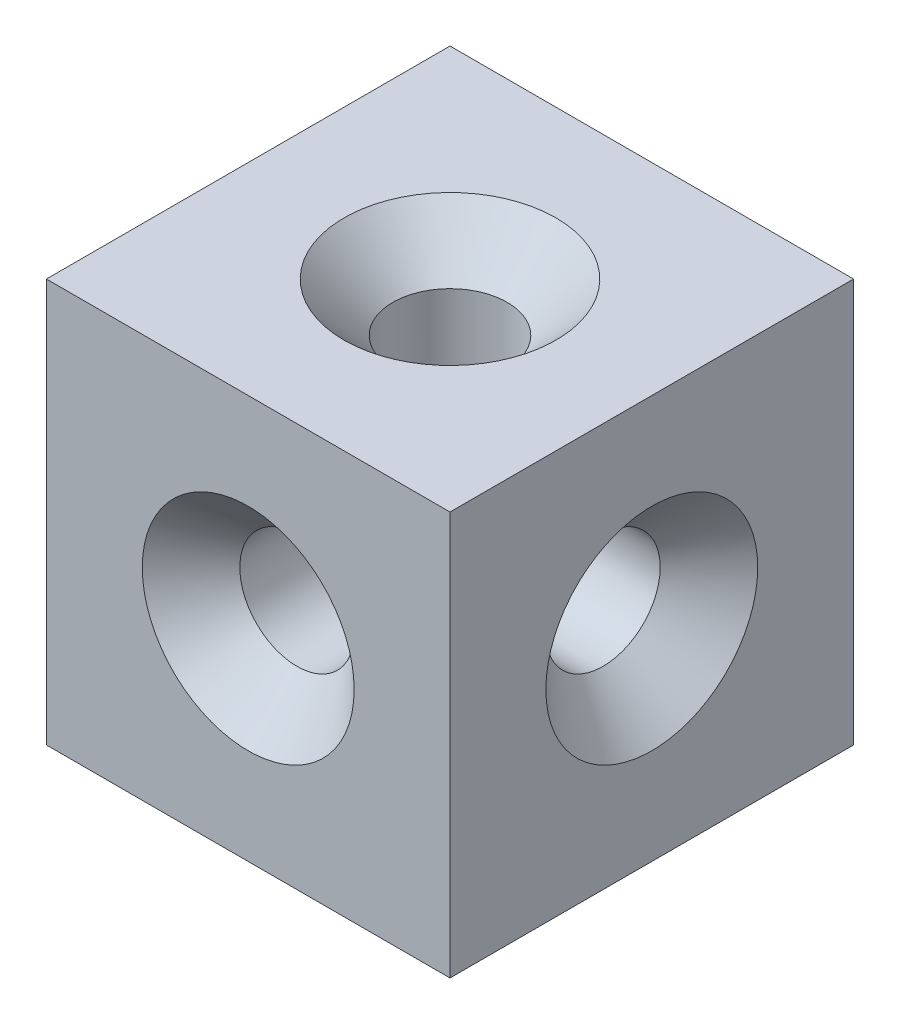
SolidWorks part; units mm, degrees
ref_plane "Front Plane" through (0, 0, 0) normal (0, 0, 1) x (1, 0, 0)
ref_plane "Top Plane" through (0, 0, 0) normal (0, 1, 0) x (1, 0, 0)
ref_plane "Right Plane" through (0, 0, 0) normal (1, 0, 0) x (0, 0, -1)
sketch "Sketch1" plane through (0, 0, 0) normal (0, 0, 1) x (1, 0, 0)
  line L1 (6, -6) -> (-6, -6)
  line L2 (6, -6) -> (6, 6)
  line L3 (6, 6) -> (-6, 6)
  line L4 (-6, -6) -> (-6, 6)
  line L5 (6, -6) -> (-6, 6) construction
  line L6 (6, 6) -> (-6, -6) construction
  point P0 (0, 0)
  dimension "D1" = 12
  dimension "D2" = 12
extrude "Boss-Extrude1" add sketch "Sketch1" along normal mid plane 12
hole_wizard "CSK for M3 Flat Head Machine Screw1" positions "Sketch3" profile "Sketch2" countersink size "M3" standard "ANSI Metric"
sketch "Sketch3" plane through (0, 0, 6) normal (0, 0, 1) x (1, 0, 0)
  point P0 (0, 0)
sketch "Sketch2" plane through (0, 0, 6) normal (1, 0, 0) x (0, -1, 0)
  line L0 (0, 0) -> (0, 7.0215)
  line L1 (0, 7.0215) -> (1.7, 6)
  line L2 (1.7, 6) -> (1.7, 1.45)
  line L3 (1.7, 1.45) -> (3.15, 0)
  line L5 (3.15, 0) -> (0, 0)
  line L6 (-1.7, 1.45) -> (-3.15, 0) construction
  line L10 (0, 7.0215) -> (-1.7, 6) construction
  line L11 (0, -6.35) -> (0, 107.95) construction
  dimension "Hole Dia." = 3.4
  dimension "Hole Depth" = 6
  dimension "Near C'Sink Dia." = 6.3
  dimension "Near C'Sink Angle" = 90
  dimension "Drill Angle" = 118
hole_wizard "CSK for M3 Flat Head Machine Screw2" positions "Sketch6" profile "Sketch7" countersink size "M3" standard "ANSI Metric"
sketch "Sketch6" plane through (6, 0, 0) normal (1, 0, 0) x (0, 0, -1)
  point P0 (0, 0)
sketch "Sketch7" plane through (6, 0, 0) normal (0, 1, 0) x (0, 0, -1)
  line L0 (0, 0) -> (0, 7.0215)
  line L1 (0, 7.0215) -> (1.7, 6)
  line L2 (1.7, 6) -> (1.7, 1.45)
  line L3 (1.7, 1.45) -> (3.15, 0)
  line L5 (3.15, 0) -> (0, 0)
  line L6 (-1.7, 1.45) -> (-3.15, 0) construction
  line L10 (0, 7.0215) -> (-1.7, 6) construction
  line L11 (0, -6.35) -> (0, 107.95) construction
  dimension "Hole Dia." = 3.4
  dimension "Hole Depth" = 6
  dimension "Near C'Sink Dia." = 6.3
  dimension "Near C'Sink Angle" = 90
  dimension "Drill Angle" = 118
hole_wizard "CSK for M3 Flat Head Machine Screw3" positions "Sketch8" profile "Sketch9" countersink size "M3" standard "ANSI Metric"
sketch "Sketch8" plane through (0, 0, -6) normal (0, 0, -1) x (-1, 0, 0)
  point P0 (0, 0)
sketch "Sketch9" plane through (0, 0, -6) normal (1, 0, 0) x (0, 1, 0)
  line L0 (0, 0) -> (0, 7.0215)
  line L1 (0, 7.0215) -> (1.7, 6)
  line L2 (1.7, 6) -> (1.7, 1.45)
  line L3 (1.7, 1.45) -> (3.15, 0)
  line L5 (3.15, 0) -> (0, 0)
  line L6 (-1.7, 1.45) -> (-3.15, 0) construction
  line L10 (0, 7.0215) -> (-1.7, 6) construction
  line L11 (0, -6.35) -> (0, 107.95) construction
  dimension "Hole Dia." = 3.4
  dimension "Hole Depth" = 6
  dimension "Near C'Sink Dia." = 6.3
  dimension "Near C'Sink Angle" = 90
  dimension "Drill Angle" = 118
hole_wizard "CSK for M3 Flat Head Machine Screw7" positions "Sketch10" profile "Sketch11" countersink size "M3" standard "ANSI Metric"
sketch "Sketch10" plane through (-6, 0, 0) normal (-1, 0, 0) x (0, 0, 1)
  point P0 (0, 0)
  point P4 (0, 0)
sketch "Sketch11" plane through (-6, 0, 0) normal (0, 1, 0) x (0, 0, 1)
  line L0 (0, 0) -> (0, 7.0215)
  line L1 (0, 7.0215) -> (1.7, 6)
  line L2 (1.7, 6) -> (1.7, 1.45)
  line L3 (1.7, 1.45) -> (3.15, 0)
  line L5 (3.15, 0) -> (0, 0)
  line L6 (-1.7, 1.45) -> (-3.15, 0) construction
  line L10 (0, 7.0215) -> (-1.7, 6) construction
  line L11 (0, -6.35) -> (0, 107.95) construction
  dimension "Hole Dia." = 3.4
  dimension "Hole Depth" = 6
  dimension "Near C'Sink Dia." = 6.3
  dimension "Near C'Sink Angle" = 90
  dimension "Drill Angle" = 118
hole_wizard "CSK for M3 Flat Head Machine Screw8" positions "Sketch12" profile "Sketch13" countersink size "M3" standard "ANSI Metric"
sketch "Sketch12" plane through (0, 6, 0) normal (0, 1, 0) x (1, 0, 0)
  point P0 (0, 0)
sketch "Sketch13" plane through (0, 6, 0) normal (1, 0, 0) x (0, 0, 1)
  line L0 (0, 0) -> (0, 7.0215)
  line L1 (0, 7.0215) -> (1.7, 6)
  line L2 (1.7, 6) -> (1.7, 1.45)
  line L3 (1.7, 1.45) -> (3.15, 0)
  line L5 (3.15, 0) -> (0, 0)
  line L6 (-1.7, 1.45) -> (-3.15, 0) construction
  line L10 (0, 7.0215) -> (-1.7, 6) construction
  line L11 (0, -6.35) -> (0, 107.95) construction
  dimension "Hole Dia." = 3.4
  dimension "Hole Depth" = 6
  dimension "Near C'Sink Dia." = 6.3
  dimension "Near C'Sink Angle" = 90
  dimension "Drill Angle" = 118
hole_wizard "CSK for M3 Flat Head Machine Screw9" positions "Sketch14" profile "Sketch15" countersink size "M3" standard "ANSI Metric"
sketch "Sketch14" plane through (0, -6, 0) normal (0, -1, 0) x (-1, 0, 0)
  point P0 (0, 0)
sketch "Sketch15" plane through (0, -6, 0) normal (1, 0, 0) x (0, 0, -1)
  line L0 (0, 0) -> (0, 7.0215)
  line L1 (0, 7.0215) -> (1.7, 6)
  line L2 (1.7, 6) -> (1.7, 1.45)
  line L3 (1.7, 1.45) -> (3.15, 0)
  line L5 (3.15, 0) -> (0, 0)
  line L6 (-1.7, 1.45) -> (-3.15, 0) construction
  line L10 (0, 7.0215) -> (-1.7, 6) construction
  line L11 (0, -6.35) -> (0, 107.95) construction
  dimension "Hole Dia." = 3.4
  dimension "Hole Depth" = 6
  dimension "Near C'Sink Dia." = 6.3
  dimension "Near C'Sink Angle" = 90
  dimension "Drill Angle" = 118
equation "\"Length\"= 283mm"
equation "\"Width\"= 225mm"
equation "\"WallThickness\"= 12.5mm"
equation "\"UpperWaterJacketThickness\"= 28mm"
equation "\"SpacerHeight\"= 80.2mm"
equation "\"SpacerCornerWidth\"= 10mm"
equation "\"SpacerCornerHeight\"= 60.16mm"
equation "\"SpacerPegDiameter\"= 10mm"
equation "\"SpacerPegHeight\"= 10mm"
equation "\"TubingShort\"= 110mm"
equation "\"TubingLong\"= 175mm"
equation "\"PlateLength\"= 252mm"
equation "\"PlateWidth\"= 190mm"
equation "\"PlateHoleDiameter\"= 5.9mm"
equation "\"PlateHoleBottom\"= 2mm"
equation "\"PlateHoleSide\"= 1.55mm"
equation "\"PlateHoleSpacing\"= 3.1mm"
equation "\"PlateThickness\"= 1.55mm"
equation "\"ReservoirBottom\"= 12.5mm"
equation "\"ReservoirSupportWidth\"= 12mm"
equation "\"ReservoirSupportHeight\"= 15.1mm"
equation "\"ReservoirSupportPlacementHeight\"= 50mm"
equation "\"ReservoirHoleDiameter\"= 12.7mm"
equation "\"ReservoirHoleRight\"= 25mm"
equation "\"ReservoirHoleTop\"= \"ReservoirSupportPlacementHeight\""
equation "\"ReservoirHeight\"= 90mm"
equation "\"ReservoirPortBottom\"= 4mm"
equation "\"ReservoirPortTop\"= 10mm"
equation "\"ReservoirPortWidth\"= 101mm"
equation "\"CustomSpacerWallThickness\" = 0.375in"
equation "\"CustomSpacerHeight\"= 5in"
equation "\"CustomSpacerRodHoleHeight\"= .75in"
equation "\"CustomSpacerRodHoleDiameter\"= .3125in"
equation "\"ScrewBlockSide\"= 12mm"
equation "\"ScrewBlockUpperHeight\"= 16mm"
equation "\"ScrewBlockLowerHeight\"= 16mm"
equation "\"InternalLength\"= \"Length\" - ( 2 * \"WallThickness\" )"
equation "\"InternalWidth\"= \"Width\" - ( 2 * \"WallThickness\" )"
equation "\"CustomSpacerPegHeight\"= 1in"
equation "\"CustomSpacerScrewBore\"=3.2mm"
equation "\"CustomSpacerScrewDepth\"=10mm"
equation "\"D1@Sketch1\"=\"ScrewBlockSide\""
equation "\"D2@Sketch1\"=\"ScrewBlockSide\""
equation "\"D1@Boss-Extrude1\"=\"ScrewBlockSide\""
